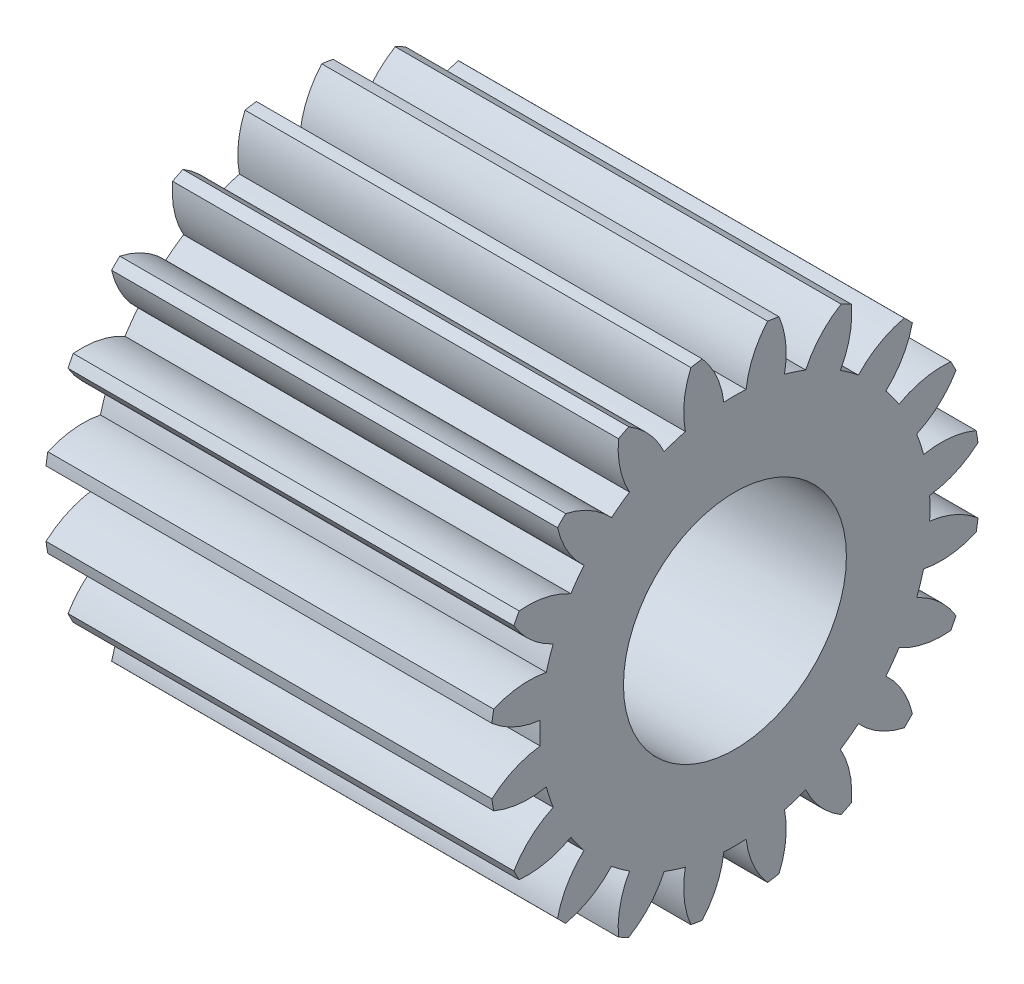
SolidWorks part; units mm, degrees
ref_plane "Plane1" through (0, 0, 0) normal (0, 0, 1) x (1, 0, 0)
ref_plane "Plane2" through (0, 0, 0) normal (0, 1, 0) x (1, 0, 0)
ref_plane "Plane3" through (0, 0, 0) normal (1, 0, 0) x (0, 0, -1)
other "Configuration Table"
sketch "HoldingSke" plane through (0, 0, 0) normal (0, 1, 0) x (1, 0, 0)
  line L0 (0, 0) -> (1.8794, -0.684)
  line L1 (-15, 0) -> (100, 0) construction
  line L2 (0, 0) -> (-2.1039, 2.3779)
  line L3 (0, 0) -> (-11.863, 4.5341)
  line L4 (0, 0) -> (8.1152, 2.9537)
  line L5 (0, 0) -> (-46.8476, -17.4728)
  line L6 (0, 0) -> (-8.2896, -5.593)
  line L7 (-2.1039, 2.3779) -> (8.6586, 51.2059)
  line L8 (-76.2, 54.61) -> (-75.3, 54.61)
  line L9 (-71.009, 38.7566) -> (-53.1078, 45.2721)
  line L10 (-76.2, 71.12) -> (104.1128, 71.12)
  line L11 (0, 0) -> (-10, 0)
  line L12 (-76.2, 101.6) -> (-76.181, 101.6)
  line L13 (24.9733, 27.94) -> (52.9518, 28.4284)
  line L14 (24.9733, 27.94) -> (24.9743, 27.94)
  line L15 (24.9733, 27.94) -> (100.4006, 29.5858)
  line L16 (-63.627, -0.5) -> (-12.827, -0.5)
  circle A0 centre (0, 0) radius 2.5
  circle A1 centre (0, 0) radius 4.374
  circle A2 centre (0, 0) radius 37.5
  circle A3 centre (0, 0) radius 2.5
  dimension "Pitch_radius" = 180.3128
sketch "BasProSke" plane through (0, 0, 0) normal (0, 1, 0) x (1, 0, 0)
  line L0 (-10, 0) -> (60, 0) construction
  line L1 (0, 0) -> (0, 5.5)
  line L2 (0, 0) -> (10, 0)
  line L3 (10, 0) -> (10, 5.5)
  line L4 (10, 5.5) -> (0, 5.5)
revolve "Base-Revolve" add sketch "BasProSke" angle 360 about L0
sketch "TooCutSke" plane through (0, 0, 0) normal (1, 0, 0) x (0, 0, -1)
  line L1 (0, 0) -> (0, 107) construction
  line L2 (0, 0) -> (-0.4255, 4.9819) construction
  line L3 (0, 0) -> (-1.5603, 9.8514) construction
  line L4 (-0.4255, 4.9819) -> (-0.7802, 4.9257) construction
  arc A0 (0.2499, 4.3669) -> (-0.2499, 4.3669) centre (0, 0) ccw
  arc A1 (0.7528, 5.4739) -> (-0.7528, 5.4739) centre (0, 0) ccw
  circle A2 centre (0, 0) radius 5 construction
  circle A3 centre (0, 0) radius 4.6985 construction
  arc A4 (-0.2499, 4.3669) -> (-0.7528, 5.4739) centre (-2.2361, 4.1322) ccw
  arc A5 (0.7528, 5.4739) -> (0.2499, 4.3669) centre (2.2361, 4.1322) ccw
extrude "ToothCut" cut sketch "TooCutSke" along normal through all
fillet "Breaks" [suppressed] radius 0.01 tangent propagation no
fillet "RootFillets" [suppressed] radius 0.126
pattern_circular "TeethCuts" count 20 every 18 about axis through (-10, 0, 0) along (1, 0, 0) of "ToothCut", "RootFillets", "Breaks"
sketch "HubNeaOneSke" plane through (0, 0, 0) normal (-1, 0, 0) x (0, 0, 1)
  circle A0 centre (0, 0) radius 4.374
extrude "HubNearOne" [suppressed] add sketch "HubNeaOneSke" along normal blind 40.0001
sketch "HubNeaBotSke" plane through (0, 0, 0) normal (-1, 0, 0) x (0, 0, 1)
  circle A0 centre (0, 0) radius 4.374
extrude "HubNearBoth" [suppressed] add sketch "HubNeaBotSke" along normal blind 20
ref_plane "FarPln" through (10, 0, 0) normal (1, 0, 0) x (0, 0, -1)
sketch "HubFarSke" plane through (10, 0, 0) normal (1, 0, 0) x (0, 0, -1)
  circle A0 centre (0, 0) radius 4.374
extrude "HubFar" [suppressed] add sketch "HubFarSke" along normal blind 20
sketch "BorSke" plane through (0, 0, 0) normal (1, 0, 0) x (0, 0, -1)
  circle A0 centre (0, 0) radius 2.5
extrude "Bore" cut sketch "BorSke" along normal mid plane 100.0001
sketch "KeySke" plane through (0, 0, 0) normal (1, 0, 0) x (0, 0, -1)
  line L0 (-1, 0) -> (-1, 3.4)
  line L1 (-1, 3.4) -> (1, 3.4)
  line L2 (1, 3.4) -> (1, 0)
  line L3 (0, 0) -> (0, 34) construction
  line L4 (-1, 0) -> (1, 0)
extrude "Keyway" [suppressed] cut sketch "KeySke" along normal mid plane 100.0001
pattern_circular "Keyway2" [suppressed] count 2 every 90 about axis through (-10, 0, 0) along (1, 0, 0) reverse direction yes
equation "' \"Module@HoldingSke\" = 6.35"
equation "' \"Num_teeth@HoldingSke\" = 12"
equation "' \"Ap@HoldingSke\" =  20"
equation "' \"Ap@HoldingSke\" = 20"
equation "' \"Width@HoldingSke\" = 0.5 * 25.4"
equation "' \"Hub_dia@HoldingSke\"= 1 * 25.4"
equation "' \"Hub_dia@HoldingSke\" = 1 * 25.4"
equation "' \"Overall_len@HoldingSke\" = 1.0 * 25.4"
equation "' \"Bore@HoldingSke\" = 0.75 * 25.4"
equation "' \"T_dim@HoldingSke\" = 0.1 * 25.4"
equation "' \"Width@KeySke\" = 0.25 * 25.4"
equation "' \"Show_teeth@HoldingSke\" = 13"
equation "' \"Backlash@HoldingSke\" = 0.009 * 25.4"
equation "' \"Addendum_fac@HoldingSke\" = 1.0"
equation "' \"Dedendum_fac@HoldingSke\" = 1.25"
equation "' \"Dedendum_add@HoldingSke\" = 0.00005 * 25.4"
equation "' \"Clearance_fac@HoldingSke\" = 0.25"
equation "\"Pitch@HoldingSke\" = 1 / \"Module@HoldingSke\""
equation "\"Overcut_dia@TooCutSke\" = (\"Num_teeth@HoldingSke\" + 2 * \"Addendum_fac@HoldingSke\") / \"Pitch@HoldingSke\" + 0.002 * 25.4"
equation "\"Pitch_dia@TooCutSke\" = \"Num_teeth@HoldingSke\" / \"Pitch@HoldingSke\""
equation "\"Base_dia@TooCutSke\" = \"Num_teeth@HoldingSke\" / \"Pitch@HoldingSke\" * cos((\"Ap@HoldingSke\"  * 3.14159265 / 180))"
equation "\"Root_dia@TooCutSke\" = (\"Num_teeth@HoldingSke\" + 2) / \"Pitch@HoldingSke\" - 2 * (\"Addendum_fac@HoldingSke\" + \"Dedendum_fac@HoldingSke\") / \"Pitch@HoldingSke\" - \"Dedendum_add@HoldingSke\" * 2"
equation "\"Half_ang@TooCutSke\" = 180 / \"Num_teeth@HoldingSke\""
equation "\"Half_CT@TooCutSke\" = \"Num_teeth@HoldingSke\" / \"Pitch@HoldingSke\" * sin((3.14159265 / 2 / \"Num_teeth@HoldingSke\")) / 2 - 7 * \"Backlash@HoldingSke\" / 4"
equation "\"Flank_rad@TooCutSke\" = \"Num_teeth@HoldingSke\" / \"Pitch@HoldingSke\" / 5"
equation "\"Radius@RootFillets\" = \"Clearance_fac@HoldingSke\" / \"Pitch@HoldingSke\" + \"Dedendum_add@HoldingSke\""
equation "\"Break_rad@Breaks\" = 0.02 / \"Pitch@HoldingSke\""
equation "\"Thickness@HoldingSke\" = \"Width@HoldingSke\""
equation "\"OAL@HoldingSke\" = \"Thickness@HoldingSke\""
equation "\"MHD@HoldingSke\" = (\"Num_teeth@HoldingSke\" + 2) / \"Pitch@HoldingSke\" - 2 * (\"Addendum_fac@HoldingSke\" + \"Dedendum_fac@HoldingSke\")  / \"Pitch@HoldingSke\" - \"Dedendum_add@HoldingSke\" * 2"
equation "\"MBD@HoldingSke\" = (\"Num_teeth@HoldingSke\" + 2) / \"Pitch@HoldingSke\" - 2 * (\"Addendum_fac@HoldingSke\" + \"Dedendum_fac@HoldingSke\")  / \"Pitch@HoldingSke\" - \"Dedendum_add@HoldingSke\" * 2 - 0.002 * 25.4"
equation "\"MHD@HoldingSke\" = ((sgn( \"MHD@HoldingSke\" - \"Hub_dia@HoldingSke\" )-1)*( \"MHD@HoldingSke\" - \"Hub_dia@HoldingSke\" ))/-2+ \"Hub_dia@HoldingSke\""
equation "\"MBD@HoldingSke\" = ((sgn( \"MBD@HoldingSke\" - \"Bore@HoldingSke\" )-1)*( \"MBD@HoldingSke\" - \"Bore@HoldingSke\" ))/-2+ \"Bore@HoldingSke\""
equation "\"OAL@HoldingSke\" = ((sgn( \"OAL@HoldingSke\" - \"Overall_len@HoldingSke\" )+1)*( \"OAL@HoldingSke\" - \"Overall_len@HoldingSke\" ))/2 + \"Overall_len@HoldingSke\" + 0.000002 * 25.4"
equation "\"Num_teeth@TeethCuts\" = int( \"Show_teeth@HoldingSke\" ) + 1"
equation "\"Num_teeth@TeethCuts\" = ((sgn( \"Num_teeth@TeethCuts\" - \"Num_teeth@HoldingSke\" )-1)*( \"Num_teeth@TeethCuts\" - \"Num_teeth@HoldingSke\" ))/-2+ \"Num_teeth@HoldingSke\""
equation "\"Num_teeth@TeethCuts\" = ((sgn( \"Num_teeth@TeethCuts\" - 2.0)+1)*( \"Num_teeth@TeethCuts\" - 2.0))/2 +2.0"
equation "\"Angle@TeethCuts\" = 360.0 / \"Num_teeth@HoldingSke\""
equation "\"Diameter@BasProSke\" = (\"Num_teeth@HoldingSke\" + 2 * \"Addendum_fac@HoldingSke\") / \"Pitch@HoldingSke\""
equation "\"Thickness@BasProSke\"  = \"Thickness@HoldingSke\""
equation "' \"Fillet_rad@BasProSke\" =  \"Thickness@HoldingSke\" * 0.05"
equation "' \"Fillet_rad@BasProSke\" = \"Thickness@HoldingSke\" * 0.05"
equation "\"MHD@HoldingSke\" = ((sgn( \"MHD@HoldingSke\" - \"Root_dia@TooCutSke\" )-1)*( \"MHD@HoldingSke\" - \"Root_dia@TooCutSke\" ))/-2+ \"Root_dia@TooCutSke\""
equation "\"Diameter@HubNeaOneSke\" = \"MHD@HoldingSke\""
equation "\"Length@HubNearOne\" = \"OAL@HoldingSke\" - \"Thickness@BasProSke\""
equation "\"Diameter@HubNeaBotSke\" = \"MHD@HoldingSke\""
equation "\"Length@HubNearBoth\" = ( \"OAL@HoldingSke\" - \"Thickness@BasProSke\" ) / 2.0"
equation "\"Thickness@FarPln\" = \"Thickness@BasProSke\""
equation "\"Diameter@HubFarSke\" = \"MHD@HoldingSke\""
equation "\"Length@HubFar\" = ( \"OAL@HoldingSke\" - \"Thickness@BasProSke\" ) / 2.0"
equation "\"Diameter@BorSke\" = \"MBD@HoldingSke\""
equation "\"D1@Bore\" = \"OAL@HoldingSke\" * 2.0"
equation "\"D1@Keyway\" = \"OAL@HoldingSke\" * 2.0"
equation "\"Offset@KeySke\" = \"T_dim@HoldingSke\" + \"MBD@HoldingSke\" / 2.0"
